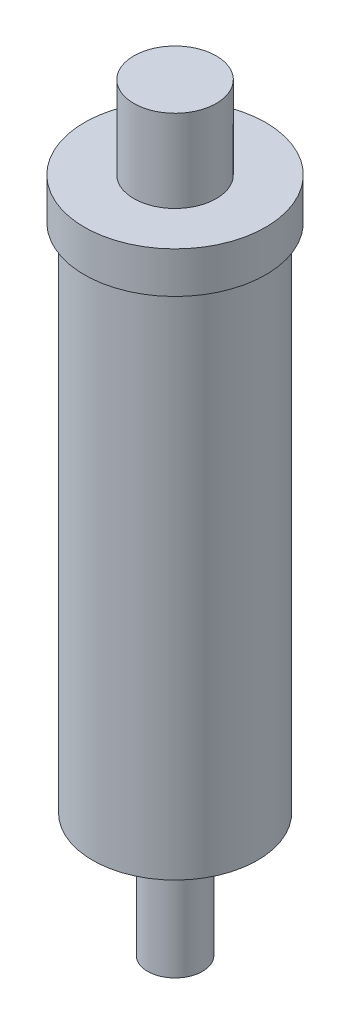
SolidWorks part; units mm, degrees
ref_plane "Front Plane" through (0, 0, 0) normal (0, 0, 1) x (1, 0, 0)
ref_plane "Top Plane" through (0, 0, 0) normal (0, 1, 0) x (1, 0, 0)
ref_plane "Right Plane" through (0, 0, 0) normal (1, 0, 0) x (0, 0, -1)
sketch "Sketch1" plane through (0, 0, 0) normal (0, 0, 1) x (1, 0, 0)
  line L0 (12.7, 170.18) -> (27.94, 170.18)
  line L1 (8.4502, 0) -> (25.4, 0)
  line L2 (0, 0) -> (0, 170.18)
  line L4 (25.4, 0) -> (25.4, 157.48)
  line L5 (25.4, 157.48) -> (27.94, 157.48)
  line L7 (0, 0) -> (0, -38.1)
  line L8 (27.94, 157.48) -> (27.94, 170.18)
  line L9 (0, -38.1) -> (8.4502, -38.1)
  line L10 (8.4502, 0) -> (8.4502, -38.1)
  line L11 (0, 170.18) -> (0, 195.58)
  line L12 (0, 195.58) -> (12.7, 195.58)
  line L13 (12.7, 170.18) -> (12.7, 195.58)
  dimension "D1" = 157.48
  dimension "D2" = 25.4
  dimension "D3" = 12.7
  dimension "D4" = 2.54
  dimension "D5" = 38.1
  dimension "D6" = 8.4502
  dimension "D7" = 12.7
  dimension "D8" = 25.4
revolve "Revolve1" add sketch "Sketch1" angle 360 about L2
sketch "Sketch2" plane through (0, -38.1, 0) normal (0, -1, 0) x (1, 0, 0)
  circle A0 centre (0, 0) radius 1.905
  dimension "D1" = 3.81
extrude "Cut-Extrude1" cut sketch "Sketch2" against normal up to surface (38.1 mm away) up to face at (0, 0, -25.4)
